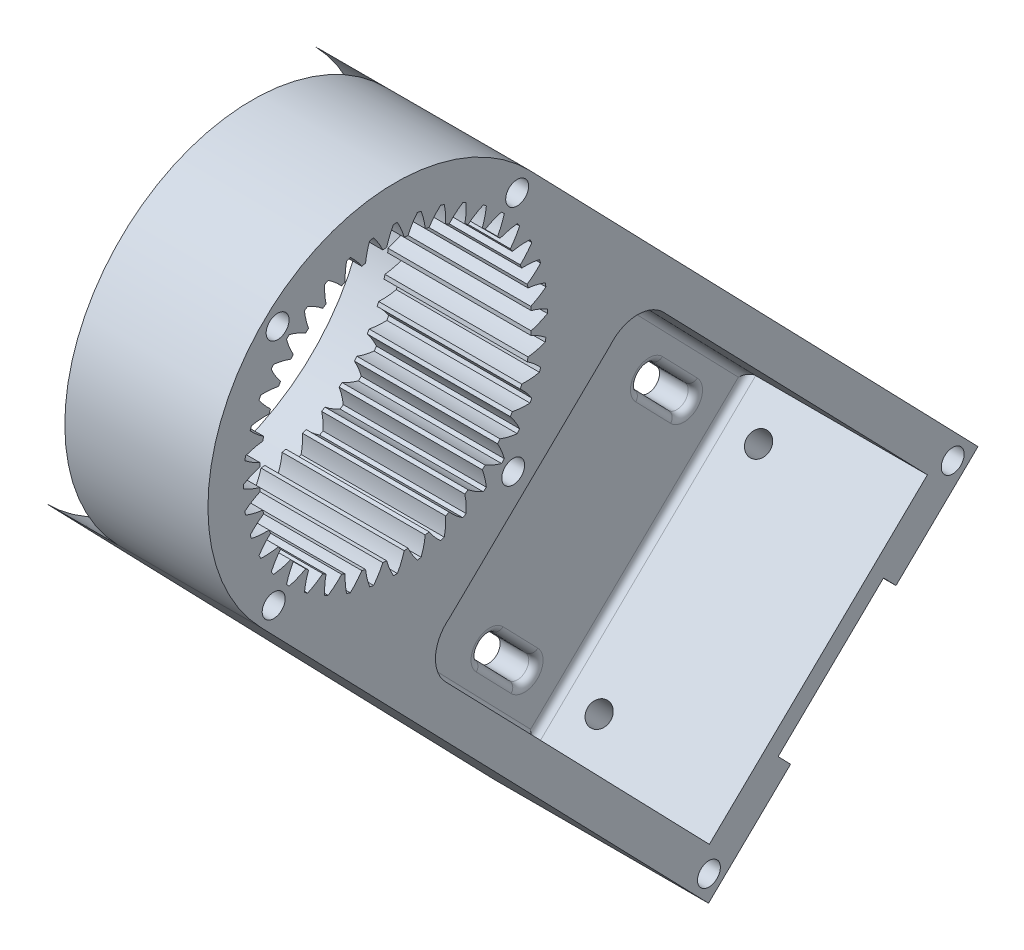
SolidWorks part; units mm, degrees
ref_plane "Plane1" through (0, 0, 0) normal (0, 0, 1) x (1, 0, 0)
ref_plane "Plane2" through (0, 0, 0) normal (0, 1, 0) x (1, 0, 0)
ref_plane "Plane3" through (0, 0, 0) normal (1, 0, 0) x (0, 0, -1)
sketch "HoldingSke" plane through (0, 0, 0) normal (0, 1, 0) x (1, 0, 0)
  line L0 (0, 0) -> (0.766, -0.6428)
  line L1 (-15, 0) -> (100, 0) construction
  line L2 (0, 0) -> (-2.1039, 2.3779)
  line L3 (0, 0) -> (-11.863, 4.5341)
  line L4 (0, 0) -> (6.6156, 5.5511)
  line L5 (0, 0) -> (-23.7986, -8.8762)
  line L6 (0, 0) -> (-10.5278, -7.1032)
  line L7 (-2.1039, 2.3779) -> (3.3635, 27.1825)
  line L8 (-76.2, 3.3779) -> (-54.61, 3.3779)
  line L9 (-71.009, 38.7566) -> (-53.1078, 45.2721)
  line L10 (-76.2, 71.12) -> (104.1128, 71.12)
  line L11 (0, 0) -> (-30, 0)
  line L12 (-76.2, 101.6) -> (-76.162, 101.6)
  line L13 (24.9733, 27.94) -> (52.9518, 28.4284)
  line L14 (24.9733, 27.94) -> (24.9743, 27.94)
  line L15 (24.9733, 27.94) -> (100.4006, 29.5858)
  circle A0 centre (0, 0) radius 26.2
  circle A1 centre (0, 0) radius 12.7
  circle A2 centre (0, 0) radius 12.7
  dimension "Num_teeth" = 40
  dimension "Pitch_radius" = 180.3128
  dimension "Width" = 30
  dimension "Diameter" = 52.4
sketch "BasProSke" plane through (0, 0, 0) normal (0, 1, 0) x (1, 0, 0)
  line L0 (-10, 0) -> (60, 0) construction
  line L1 (0, 19) -> (0, 26.2)
  line L2 (0, 19) -> (30, 19)
  line L3 (30, 19) -> (30, 26.2)
  line L4 (30, 26.2) -> (0, 26.2)
  dimension "Thickness" = 30
  dimension "Diameter" = 52.4
revolve "Base-Revolve" add sketch "BasProSke" angle 360 about L0
sketch "TooCutSke" plane through (0, 0, 0) normal (1, 0, 0) x (0, 0, -1)
  line L3 (0.8802, 19.9806) -> (0.8802, 53.6633) construction
  line L4 (0, 0) -> (0, 59.563) construction
  line L5 (0, 0) -> (-5.3609, 68.1169) construction
  line L6 (-8.4195, 16.3041) -> (36.3991, 19.8314) construction
  circle A0 centre (0, 0) radius 20 construction
  circle A1 centre (0, 0) radius 21.251 construction
  circle A2 centre (0, 0) radius 16.9145 construction
  circle A3 centre (0, 0) radius 18.9746 construction
  arc A4 (1.2283, 18.9348) -> (0.2723, 21.2493) centre (-8.4195, 16.3041) ccw
  arc A5 (1.2283, 18.9348) -> (-1.2283, 18.9348) centre (0, 0) ccw
  arc A6 (0.2723, 21.2493) -> (-0.2723, 21.2493) centre (0, 0) ccw
  arc A7 (-0.2723, 21.2493) -> (-1.2283, 18.9348) centre (8.4195, 16.3041) ccw
extrude "ToothCut" cut sketch "TooCutSke" along normal through all
fillet "Breaks" [suppressed] radius 0.1
fillet "RootFillets" [suppressed] radius 0.251
pattern_circular "TeethCuts" count 40 every 9 about axis through (-10, 0, 0) along (1, 0, 0) of "RootFillets", "Breaks", "ToothCut"
sketch "Sketch3" plane through (0, 0, 0) normal (-1, 0, 0) x (0, 0, 1)
  line L3 (-43.8707, -75.8274) -> (15.2355, -14.7418)
  line L4 (-15.2355, 14.7418) -> (-74.3417, -46.3438)
  line L5 (-74.3417, -46.3438) -> (-43.8707, -75.8274)
  line L6 (-43.8707, -75.8274) -> (4.5304, -25.8053)
  line L7 (-69.9493, -57.5514) -> (-68.2109, -55.7548)
  line L8 (-81.4118, -46.4603) -> (-69.9493, -57.5514)
  line L9 (-18.8287, 18.2186) -> (-81.4118, -46.4603)
  line L10 (-43.7543, -82.8975) -> (18.8287, -18.2186)
  line L11 (-55.2169, -71.8064) -> (-43.7543, -82.8975)
  line L12 (-53.4784, -70.0098) -> (-55.2169, -71.8064)
  line L13 (-68.2109, -55.7548) -> (-53.4784, -70.0098)
  line L14 (-69.9493, -57.5514) -> (-68.2109, -55.7548)
  line L15 (-81.4118, -46.4603) -> (-69.9493, -57.5514)
  line L16 (-18.8287, 18.2186) -> (-81.4118, -46.4603)
  line L17 (-43.7543, -82.8975) -> (18.8287, -18.2186)
  line L18 (-55.2169, -71.8064) -> (-43.7543, -82.8975)
  line L19 (-53.4784, -70.0098) -> (-55.2169, -71.8064)
  line L20 (-68.2109, -55.7548) -> (-53.4784, -70.0098)
  line L21 (-25.9405, 3.6782) -> (-74.3417, -46.3438)
  line L22 (-74.3417, -46.3438) -> (-43.8707, -75.8274)
  circle A0 centre (0, 0) radius 26.2 construction
  arc A1 (18.8287, -18.2186) -> (-18.8287, 18.2186) centre (0, 0) ccw
  arc A3 (15.2355, -14.7418) -> (-15.2355, 14.7418) centre (0, 0) ccw
  arc A5 (-18.8287, 18.2186) -> (-25.9405, 3.6782) centre (0, 0) ccw
  arc A6 (4.5304, -25.8053) -> (18.8287, -18.2186) centre (0, 0) ccw
  dimension "D1" = 0
  dimension "D2" = 0
extrude "Boss-Extrude1" add sketch "Sketch3" against normal up to surface (30 mm away) up to face at (30, 0, 26.2)
sketch "Sketch4" plane through (0, 0, 0) normal (-1, 0, 0) x (0, 0, 1)
  line L0 (4.5304, -25.8053) -> (-43.8707, -75.8274) construction
  line L1 (4.5304, -25.8053) -> (-43.8707, -75.8274)
  line L10 (4.5304, -25.8053) -> (-43.8707, -75.8274)
  line L11 (-43.8707, -75.8274) -> (-74.3417, -46.3438)
  line L12 (-74.3417, -46.3438) -> (-25.9405, 3.6782)
  line L13 (-18.8287, 18.2186) -> (-81.4118, -46.4603)
  line L14 (-81.4118, -46.4603) -> (-69.9493, -57.5514)
  line L15 (-69.9493, -57.5514) -> (-68.2109, -55.7548)
  line L16 (-68.2109, -55.7548) -> (-53.4784, -70.0098)
  line L17 (-53.4784, -70.0098) -> (-55.2169, -71.8064)
  line L18 (-55.2169, -71.8064) -> (-43.7543, -82.8975)
  line L19 (-43.7543, -82.8975) -> (18.8287, -18.2186)
  line L21 (-43.8707, -75.8274) -> (-74.3417, -46.3438)
  line L22 (-74.3417, -46.3438) -> (-25.9405, 3.6782)
  arc A0 (-25.9405, 3.6782) -> (4.5304, -25.8053) centre (0, 0) ccw construction
  arc A1 (-25.9405, 3.6782) -> (4.5304, -25.8053) centre (0, 0) ccw
  arc A2 (-18.8287, 18.2186) -> (-25.9405, 3.6782) centre (0, 0) ccw
  arc A3 (4.5304, -25.8053) -> (18.8287, -18.2186) centre (0, 0) ccw
  dimension "D1" = 0
extrude "Boss-Extrude2" add sketch "Sketch4" against normal blind 5
sketch "Sketch5" plane through (0, 0, 0) normal (-1, 0, 0) x (0, 0, 1)
  circle A1 centre (0, 0) radius 26.2
extrude "Cut-Extrude2" cut sketch "Sketch5" against normal blind 10
sketch "Sketch6" plane through (5, 0, 0) normal (1, 0, 0) x (0, 0, -1)
  line L0 (25.9405, 3.6782) -> (74.3417, -46.3438) construction
  line L1 (43.8707, -75.8274) -> (-4.5304, -25.8053) construction
  line L2 (25.9405, 3.6782) -> (31.1532, -1.709)
  line L3 (0.6822, -31.1925) -> (-4.5304, -25.8053)
  arc A0 (-4.5304, -25.8053) -> (25.9405, 3.6782) centre (0, 0) ccw construction
  arc A1 (-4.5304, -25.8053) -> (25.9405, 3.6782) centre (0, 0) ccw
  arc A2 (0.6822, -31.1925) -> (31.1532, -1.709) centre (0, 0) ccw
  arc A3 (-5.395, -30.73) -> (30.891, 4.3802) centre (0, 0) ccw construction
  dimension "D1" = 5
extrude "Boss-Extrude3" add sketch "Sketch6" along normal up to surface (25 mm away) up to face at (30, -38.0159, -36.784)
sketch "Sketch7" plane through (30, 0, 0) normal (1, 0, 0) x (0, 0, -1)
  line L1 (7.5523, -30.2721) -> (30.007, -8.545)
  arc A0 (0.6822, -31.1925) -> (31.1532, -1.709) centre (0, 0) ccw construction
  arc A1 (7.5523, -30.2721) -> (30.007, -8.545) centre (0, 0) ccw
extrude "Cut-Extrude3" cut sketch "Sketch7" against normal up to surface (25 mm away) up to face at (5, -40.261, -38.9564)
fillet "Fillet1" radius 5 2 edges at (17.5, -1.709, -31.1532) (17.5, -31.1925, -0.6822)
sketch "Sketch8" plane through (0, 0, 0) normal (-1, 0, 0) x (0, 0, 1)
  line L0 (-38.8889, -18.0447) -> (-43.7565, -23.0753) construction
  line L1 (-16.6106, -39.6011) -> (-21.4782, -44.6316) construction
  line L2 (-15.4608, -40.7136) -> (-20.3283, -45.7442)
  line L3 (-17.7605, -38.4885) -> (-22.628, -43.5191)
  line L5 (-65.3129, -45.3535) -> (-60.4453, -40.323) construction
  line L7 (-40.0387, -16.9321) -> (-44.9063, -21.9627)
  line L8 (-37.739, -19.1573) -> (-42.6066, -24.1878)
  line L9 (-66.4627, -44.241) -> (-61.5951, -39.2104)
  line L10 (-64.163, -46.4661) -> (-59.2954, -41.4356)
  line L11 (-43.0346, -66.9099) -> (-38.167, -61.8794) construction
  line L12 (-41.8847, -68.0225) -> (-37.0171, -62.9919)
  line L13 (-44.1844, -65.7973) -> (-39.3168, -60.7668)
  arc A4 (-15.4608, -40.7136) -> (-17.7605, -38.4885) centre (-16.6106, -39.6011) ccw
  arc A5 (-22.628, -43.5191) -> (-20.3283, -45.7442) centre (-21.4782, -44.6316) ccw
  arc A6 (-40.0387, -16.9321) -> (-37.739, -19.1573) centre (-38.8889, -18.0447) cw
  arc A7 (-42.6066, -24.1878) -> (-44.9063, -21.9627) centre (-43.7565, -23.0753) cw
  arc A8 (-66.4627, -44.241) -> (-64.163, -46.4661) centre (-65.3129, -45.3535) ccw
  arc A9 (-59.2954, -41.4356) -> (-61.5951, -39.2104) centre (-60.4453, -40.323) ccw
  arc A10 (-41.8847, -68.0225) -> (-44.1844, -65.7973) centre (-43.0346, -66.9099) cw
  arc A11 (-39.3168, -60.7668) -> (-37.0171, -62.9919) centre (-38.167, -61.8794) cw
  point P3 (-40.9617, -42.4773)
  point P7 (-19.0444, -42.1164)
  point P10 (-41.3227, -20.56)
  point P13 (-62.8791, -42.8383)
  point P14 (-40.9617, -42.4773)
  point P29 (-40.6008, -64.3946)
extrude "Cut-Extrude4" cut sketch "Sketch8" against normal through all
sketch "Sketch9" plane through (0, 0, 0) normal (-1, 0, 0) x (0, 0, 1)
  circle A0 centre (-60.5861, -29.2475) radius 1
  circle A5 centre (-51.2751, -31.1333) radius 1
extrude "Cut-Extrude5" cut sketch "Sketch9" against normal blind 2
sketch "Sketch11" plane through (30, 0, 0) normal (1, 0, 0) x (0, 0, -1)
  circle A0 centre (43.8125, -79.3625) radius 1.6
  circle A1 centre (77.8768, -46.4021) radius 1.6
extrude "Cut-Extrude7" cut sketch "Sketch11" against normal through all
fillet "Fillet2" radius 1 22 edges at (5, -61.0856, -59.1062) (5, -56.7735, -25.4343) (5, -33.8715, -5.6049) (5, -19.4086, -18.7797) (5, -6.7172, -33.6686) (5, -27.2899, -55.9052) (5, -60.7295, -37.0544) (5, -65.5072, -39.4509) (5, -68.0598, -44.1471) (5, -63.2821, -41.7506) (5, -39.1731, -59.3327) (5, -43.9508, -61.7292) (5, -46.5034, -66.4254) (5, -41.7257, -64.0289) (5, -24.2251, -44.8691) (5, -19.4474, -42.4725) (5, -16.8948, -37.7763) (5, -21.6726, -40.1728) (5, -45.7815, -22.5908) (5, -41.0038, -20.1942) (5, -38.4512, -15.498) (5, -43.2289, -17.8945)
sketch "Sketch1" plane through (30, 0, 0) normal (1, 0, 0) x (0, 0, -1)
  circle A5 centre (16.4611, -17.0124) radius 1.6
  circle A6 centre (-17.0124, -16.4611) radius 1.6
  circle A7 centre (-16.4611, 17.0124) radius 1.6
  circle A8 centre (17.0124, 16.4611) radius 1.6
  point P13 (0, 0)
  dimension "D1" = 4
extrude "Cut-Extrude1" cut sketch "Sketch1" against normal through all
sketch "Sketch12" plane through (0, -64.6789, -62.5831) normal (0, -0.7187, -0.6954) x (1, 0, 0)
  circle A1 centre (10.5, 15.5) radius 1.6
  circle A2 centre (10.5, 15.5) radius 1.6
  circle A3 centre (10.5, -15.5) radius 1.6
  circle A4 centre (10.5, -15.5) radius 1.6
  dimension "D1" = 0
  dimension "D2" = 0
extrude "Cut-Extrude8" cut sketch "Sketch12" against normal blind 10
sketch "Sketch13" plane through (5, 0, 0) normal (1, 0, 0) x (0, 0, -1)
  line L3 (19.8418, -27.823) -> (17.7613, -25.6616)
  line L4 (21.2557, -27.85) -> (27.0194, -22.302)
  line L5 (17.7882, -24.2477) -> (23.5519, -18.6997)
  line L6 (27.0464, -20.8881) -> (24.9659, -18.7267)
  arc A0 (19.8418, -27.823) -> (21.2557, -27.85) centre (20.5622, -27.1295) ccw
  arc A1 (27.0194, -22.302) -> (27.0464, -20.8881) centre (26.3259, -21.5816) ccw
  arc A2 (24.9659, -18.7267) -> (23.5519, -18.6997) centre (24.2454, -19.4202) ccw
  arc A3 (17.7613, -25.6616) -> (17.7882, -24.2477) centre (18.4817, -24.9681) cw
  point P6 (22.4034, -23.2746)
  point P7 (22.4038, -23.2748)
  dimension "D1" = 1
extrude "Cut-Extrude9" cut sketch "Sketch13" against normal through all
equation "' \"Module@HoldingSke\" = 6.35"
equation "' \"Num_teeth@HoldingSke\" = 24"
equation "' \"Ap@HoldingSke\" =  14.5"
equation "' \"Ap@HoldingSke\" = 14.5"
equation "' \"Width@HoldingSke\" = 12"
equation "' \"Diameter@HoldingSke\" = 8 * 25.4"
equation "' \"Show_teeth@HoldingSke\" = 100"
equation "' \"Backlash@HoldingSke\" = 0.009 * 25.4"
equation "' \"Addendum_fac@HoldingSke\" = 1.0"
equation "' \"Dedendum_fac@HoldingSke\" = 1.25"
equation "' \"Dedendum_add@HoldingSke\" = 0.00005 * 25.4"
equation "' \"Clearance_fac@HoldingSke\" = 0.25"
equation "\"Pitch@HoldingSke\" = 1 / \"Module@HoldingSke\" "
equation "\"Overcut_dia@TooCutSke\" = (\"Num_teeth@HoldingSke\" - 2 * \"Addendum_fac@HoldingSke\") / \"Pitch@HoldingSke\" - 0.002 * 25.4"
equation "\"Pitch_dia@TooCutSke\" = \"Num_teeth@HoldingSke\" / \"Pitch@HoldingSke\""
equation "\"Base_dia@TooCutSke\" = \"Num_teeth@HoldingSke\" / \"Pitch@HoldingSke\" * cos((\"Ap@HoldingSke\"  * 3.14159265 / 180)) * 0.90"
equation "\"Root_dia@TooCutSke\" = \"Num_teeth@HoldingSke\"  / \"Pitch@HoldingSke\" + 2 *  \"Dedendum_fac@HoldingSke\"/ \"Pitch@HoldingSke\" + \"Dedendum_add@HoldingSke\" * 2"
equation "\"Half_ang@TooCutSke\" = 180 / \"Num_teeth@HoldingSke\""
equation "\"Half_CT@TooCutSke\" = \"Num_teeth@HoldingSke\" / \"Pitch@HoldingSke\" * sin((3.14159265 / 2 / \"Num_teeth@HoldingSke\")) / 2 + 10 * \"Backlash@HoldingSke\" / 4"
equation "\"Flank_rad@TooCutSke\" = \"Num_teeth@HoldingSke\" / \"Pitch@HoldingSke\" / 4"
equation "\"Radius@RootFillets\"= \"Clearance_fac@HoldingSke\" / \"Pitch@HoldingSke\" + \"Dedendum_add@HoldingSke\""
equation "\"Break_rad@Breaks\" = 0.02 / \"Pitch@HoldingSke\" * 5"
equation "\"Num_teeth@TeethCuts\" = int( \"Show_teeth@HoldingSke\" ) + 1"
equation "\"Num_teeth@TeethCuts\" = ((sgn( \"Num_teeth@TeethCuts\" - \"Num_teeth@HoldingSke\" )-1)*( \"Num_teeth@TeethCuts\" - \"Num_teeth@HoldingSke\" ))/-2+ \"Num_teeth@HoldingSke\""
equation "\"Num_teeth@TeethCuts\" = ((sgn( \"Num_teeth@TeethCuts\" - 2.0)+1)*( \"Num_teeth@TeethCuts\" - 2.0))/2 +2.0"
equation "\"Angle@TeethCuts\" = 360.0 / \"Num_teeth@HoldingSke\""
equation "\"Diameter@BasProSke\" = \"Num_teeth@HoldingSke\"  / \"Pitch@HoldingSke\" + 2 *  \"Dedendum_fac@HoldingSke\"/ \"Pitch@HoldingSke\" + \"Dedendum_add@HoldingSke\" * 2 + 0.002 * 25.4"
equation "\"Diameter@BasProSke\" = ((sgn( \"Diameter@BasProSke\"  - \"Diameter@HoldingSke\" )+1)*( \"Diameter@BasProSke\"  - \"Diameter@HoldingSke\" ))/2 + \"Diameter@HoldingSke\""
equation "\"Inside_diameter@BasProSke\" =  (\"Num_teeth@HoldingSke\" - 2 * \"Addendum_fac@HoldingSke\") / \"Pitch@HoldingSke\" "
equation "\"Thickness@BasProSke\"  = \"Width@HoldingSke\""
